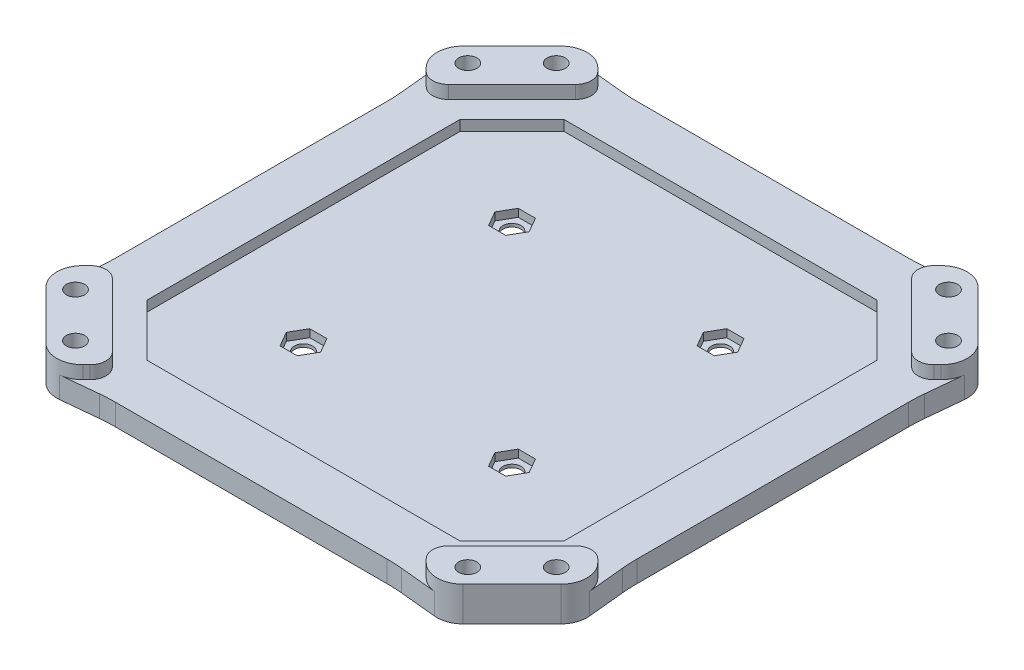
SolidWorks part; units mm, degrees
material "PP Copolymer"
ref_plane "Front Plane" through (0, 0, 0) normal (0, 0, 1) x (1, 0, 0)
ref_plane "Top Plane" through (0, 0, 0) normal (0, 1, 0) x (1, 0, 0)
ref_plane "Right Plane" through (0, 0, 0) normal (1, 0, 0) x (0, 0, -1)
sketch "Sketch1" plane through (0, 0, 0) normal (0, 1, 0) x (1, 0, 0)
  line L0 (50, 0) -> (-50, 0) construction
  line L1 (-50, -50) -> (50, -50) construction
  line L2 (-50, -50) -> (-50, 50) construction
  line L3 (-50, 50) -> (50, 50) construction
  line L4 (50, -50) -> (50, 50) construction
  line L5 (50, 50) -> (44.6967, 44.6967) construction
  line L6 (-50, 50) -> (50, -50) construction
  line L7 (0, 50) -> (0, -50) construction
  line L8 (-27.5164, 50) -> (27.5164, 50)
  line L9 (50, 27.5164) -> (50, -27.5164)
  line L10 (27.5164, -50) -> (-27.5164, -50)
  line L11 (-50, -27.5164) -> (-50, 27.5164)
  line L12 (37.6256, 46.1109) -> (46.1109, 37.6256) construction
  line L13 (38.3327, 51.0607) -> (51.0607, 38.3327)
  line L14 (27.5164, 50) -> (38.3327, 51.0607)
  line L15 (50, 27.5164) -> (51.0607, 38.3327)
  line L16 (50, -27.5164) -> (51.0607, -38.3327)
  line L17 (51.0607, -38.3327) -> (38.3327, -51.0607)
  line L18 (27.5164, -50) -> (38.3327, -51.0607)
  line L19 (-27.5164, -50) -> (-38.3327, -51.0607)
  line L20 (-38.3327, -51.0607) -> (-51.0607, -38.3327)
  line L21 (-50, -27.5164) -> (-51.0607, -38.3327)
  line L22 (-50, 27.5164) -> (-51.0607, 38.3327)
  line L23 (-51.0607, 38.3327) -> (-38.3327, 51.0607)
  line L24 (-27.5164, 50) -> (-38.3327, 51.0607)
  line L25 (41.8683, 41.8683) -> (44.6967, 44.6967) construction
  circle A0 centre (37.6256, 46.1109) radius 1.75
  circle A1 centre (46.1109, 37.6256) radius 1.75
  circle A2 centre (37.6256, -46.1109) radius 1.75
  circle A3 centre (46.1109, -37.6256) radius 1.75
  circle A4 centre (-46.1109, -37.6256) radius 1.75
  circle A5 centre (-37.6256, -46.1109) radius 1.75
  circle A6 centre (-37.6256, 46.1109) radius 1.75
  circle A7 centre (-46.1109, 37.6256) radius 1.75
  point P0 (0, 0)
  point P15 (0, 0)
  point P18 (0, 0)
  point P21 (0, 0)
  point P24 (0, 0)
  point P58 (0, 0)
  dimension "D12" = 3.5
  dimension "D3" = 92.2218
  dimension "D7" = 12
  dimension "D14" = 75.2513
  dimension "D15" = 75.2513
  dimension "D6" = 75.2513
  dimension "D1" = 100
  dimension "D2" = 100
  dimension "D4" = 7.5
  dimension "D5" = 45
  dimension "D8" = 12
  dimension "D9" = 18
  dimension "D10" = 4
  dimension "D11" = 18
  dimension "D13" = 5.601
extrude "Boss-Extrude1" add sketch "Sketch1" along normal blind 4.1 contours L8 L24 L23 L22 L11 L21 L20 L19 L10 L18 L17 L16 L9 L15 L13 L14 A7 A6 A5 A4 A3 A2 A1 A0 region at (0, 0, 0)
sketch "Sketch2" plane through (0, 4.1, 0) normal (0, 1, 0) x (1, 0, 0)
  line L0 (0, 0) -> (0, 40) construction
  line L2 (0, 0) -> (-40, 0) construction
  line L4 (-40, -30) -> (-40, 30)
  line L5 (-40, 30) -> (-30, 40)
  line L6 (-30, 40) -> (30, 40)
  line L7 (30, 40) -> (40, 30)
  line L8 (40, 30) -> (40, -30)
  line L9 (40, -30) -> (30, -40)
  line L10 (30, -40) -> (-30, -40)
  line L11 (-30, -40) -> (-40, -30)
  dimension "D1" = 80
  dimension "D2" = 80
  dimension "D3" = 45
  dimension "D4" = 90
  dimension "D5" = 60
  dimension "D6" = 45
extrude "Cut-Extrude1" cut sketch "Sketch2" against normal blind 2
sketch "Sketch3" plane through (0, 2.1, 0) normal (0, 1, 0) x (1, 0, 0)
  line L0 (0, 0) -> (-34, 0) construction
  line L18 (-29.0716, 13.612) -> (-21.0716, 6.8992)
  line L19 (-20, 4.6011) -> (-20, -4.6011)
  line L20 (-21.0716, -6.8992) -> (-29.0716, -13.612)
  line L21 (-34, 11.3139) -> (-34, -11.3139)
  line L22 (34, -11.3139) -> (34, 11.3139)
  line L23 (21.0716, 6.8992) -> (29.0716, 13.612)
  line L24 (20, -4.6011) -> (20, 4.6011)
  line L25 (29.0716, -13.612) -> (21.0716, -6.8992)
  line L26 (-14, -21.4596) -> (14, -21.4596)
  line L27 (9.5853, -8.5313) -> (16.2981, -16.5313)
  line L28 (-7.2872, -7.4596) -> (7.2872, -7.4596)
  line L29 (-16.2981, -16.5313) -> (-9.5853, -8.5313)
  line L30 (0, 10.4596) -> (0, -10.4596) construction
  line L31 (7.2872, -10.4596) -> (-7.2872, -10.4596) construction
  line L32 (7.2872, 10.4596) -> (-7.2872, 10.4596) construction
  line L33 (-16.2981, 16.5313) -> (-9.5853, 8.5313)
  line L34 (-7.2872, 7.4596) -> (7.2872, 7.4596)
  line L35 (9.5853, 8.5313) -> (16.2981, 16.5313)
  line L36 (-14, 21.4596) -> (14, 21.4596)
  line L37 (0, -10.4596) -> (0, -21.4596) construction
  arc A16 (-29.0716, -13.612) -> (-34, -11.3139) centre (-31, -11.3139) cw
  arc A17 (-20, -4.6011) -> (-21.0716, -6.8992) centre (-23, -4.6011) cw
  arc A18 (-21.0716, 6.8992) -> (-20, 4.6011) centre (-23, 4.6011) cw
  arc A19 (-29.0716, 13.612) -> (-34, 11.3139) centre (-31, 11.3139) ccw
  arc A20 (29.0716, -13.612) -> (34, -11.3139) centre (31, -11.3139) ccw
  arc A21 (29.0716, 13.612) -> (34, 11.3139) centre (31, 11.3139) cw
  arc A22 (20, 4.6011) -> (21.0716, 6.8992) centre (23, 4.6011) cw
  arc A23 (21.0716, -6.8992) -> (20, -4.6011) centre (23, -4.6011) cw
  arc A24 (-16.2981, -16.5313) -> (-14, -21.4596) centre (-14, -18.4596) ccw
  arc A25 (16.2981, -16.5313) -> (14, -21.4596) centre (14, -18.4596) cw
  arc A26 (7.2872, -7.4596) -> (9.5853, -8.5313) centre (7.2872, -10.4596) cw
  arc A27 (-9.5853, -8.5313) -> (-7.2872, -7.4596) centre (-7.2872, -10.4596) cw
  arc A28 (-9.5853, 8.5313) -> (-7.2872, 7.4596) centre (-7.2872, 10.4596) ccw
  arc A29 (7.2872, 7.4596) -> (9.5853, 8.5313) centre (7.2872, 10.4596) ccw
  arc A30 (16.2981, 16.5313) -> (14, 21.4596) centre (14, 18.4596) ccw
  arc A31 (-16.2981, 16.5313) -> (-14, 21.4596) centre (-14, 18.4596) cw
  point P53 (0, 0)
  point P57 (0, 0)
  dimension "D3" = 14
  dimension "D2" = 3
  dimension "D1" = 20
  dimension "D4" = 100
  dimension "D5" = 9.2022
  dimension "D6" = 50
  dimension "D7" = 46
  dimension "D8" = 62
  dimension "D9" = 62
  dimension "D10" = 50
  dimension "D11" = 7.4596
  dimension "D12" = 28
  dimension "D13" = 22.6277
extrude "Cut-Extrude2" [suppressed] cut sketch "Sketch3" against normal blind 1.5
sketch "Sketch4" plane through (0, 2.1, 0) normal (0, 1, 0) x (1, 0, 0)
  line L1 (0, 0) -> (30, 0) construction
  line L2 (0, 0) -> (0, 30) construction
  line L3 (0, 30) -> (30, 30) construction
  line L4 (30, 0) -> (30, 30) construction
  circle A0 centre (30, 30) radius 1.75
  dimension "D2" = 3.5
  dimension "D1" = 30
  dimension "D3" = 30
extrude "Cut-Extrude3" [suppressed] cut sketch "Sketch4" against normal through all
sketch "Sketch5" [suppressed] plane through (0, 2.1, 0) normal (0, 1, 0) x (1, 0, 0)
  circle A0 centre (30, 30) radius 4
  circle A1 centre (30, 30) radius 1.75 construction
  circle A2 centre (30, 30) radius 1.75
  dimension "D1" = 8
extrude "Boss-Extrude2" [suppressed] add sketch "Sketch5" along normal blind 1.5
ref_axis "Axis1" through (0, 4.2, 0) along (0, -1, 0)
fillet "Fillet2" radius 30 8 edges at (-50, 2.05, 27.5164) (-50, 2.05, -27.5164) (-27.5164, 2.05, -50) (27.5164, 2.05, -50) (50, 2.05, -27.5164) (50, 2.05, 27.5164) (-27.5164, 2.05, 50) (27.5164, 2.05, 50)
sketch "Sketch7" plane through (0, 2.1, 0) normal (0, 1, 0) x (1, 0, 0)
  line L1 (-10, -10) -> (10, -10)
  line L2 (-10, -10) -> (-10, 10)
  line L3 (-10, 10) -> (10, 10)
  line L4 (10, -10) -> (10, 10)
  line L5 (-10, -10) -> (10, 10) construction
  line L6 (-10, 10) -> (10, -10) construction
  point P0 (0, 0)
  dimension "D1" = 20
  dimension "D2" = 20
extrude "Cut-Extrude5" [suppressed] cut sketch "Sketch7" against normal through all
mirror "Simetría1" [suppressed] about plane through (0, 0, 0) normal (1, 0, 0)
mirror "Simetría2" [suppressed] about plane through (0, 0, 0) normal (0, 0, 1)
fillet "Redondeo1" [suppressed] radius 2
fillet "Redondeo2" radius 5 8 edges at (-38.3327, 2.05, 51.0607) (38.3327, 2.05, 51.0607) (51.0607, 2.05, 38.3327) (51.0607, 2.05, -38.3327) (38.3327, 2.05, -51.0607) (-51.0607, 2.05, 38.3327) (-51.0607, 2.05, -38.3327) (-38.3327, 2.05, -51.0607)
sketch "Croquis1" plane through (0, 4.1, 0) normal (0, 1, 0) x (1, 0, 0)
  line L0 (-18.4123, -17.25) -> (-16.8246, -20) construction
  line L1 (-23.1754, -20) -> (-21.5877, -22.75) construction
  line L2 (-18.4123, -17.25) -> (-21.5877, -17.25) construction
  line L3 (-21.5877, -17.25) -> (-23.1754, -20) construction
  line L4 (-21.5877, -22.75) -> (-18.4123, -22.75) construction
  line L5 (-18.4123, -22.75) -> (-16.8246, -20) construction
  line L6 (-18.4123, -22.75) -> (-21.5877, -17.25) construction
  line L7 (-18.4123, -17.25) -> (-21.5877, -22.75) construction
  line L8 (-16.8246, -20) -> (-23.1754, -20) construction
  line L9 (-18.3546, -17.15) -> (-16.7091, -20)
  line L10 (-18.3546, -22.85) -> (-16.7091, -20)
  line L11 (-21.6454, -22.85) -> (-18.3546, -22.85)
  line L12 (-23.2909, -20) -> (-21.6454, -22.85)
  line L13 (-21.6454, -17.15) -> (-23.2909, -20)
  line L14 (-18.3546, -17.15) -> (-21.6454, -17.15)
  point P3 (-20, -20)
  dimension "D1" = 3.1754
  dimension "D2" = 5.5
  dimension "D3" = 20
  dimension "D4" = 3.2909
  dimension "D5" = 6.5818
  dimension "D6" = 0.1
  dimension "D7" = 20
extrude "Cortar-Extruir1" cut sketch "Croquis1" against normal blind 3.5
mirror "Simetría3" about plane through (0, 0, 0) normal (1, 0, 0) of "Cortar-Extruir1"
mirror "Simetría4" about plane through (0, 0, 0) normal (0, 0, 1) of "Simetría3"
sketch "Croquis2" plane through (0, 2.1, 0) normal (0, 1, 0) x (1, 0, 0)
  line L0 (0, 0) -> (0, -20) construction
  circle A0 centre (-20, -20) radius 1.75
  circle A1 centre (-20, 20) radius 1.75
  circle A2 centre (20, 20) radius 1.75
  circle A3 centre (20, -20) radius 1.75
  dimension "D1" = 40
  dimension "D3" = 3.5
  dimension "D2" = 40
extrude "Cortar-Extruir2" cut sketch "Croquis2" against normal blind 2.5
sketch "Croquis3" plane through (0, 4.1, 0) normal (0, 1, 0) x (1, 0, 0)
  line L0 (-49.3894, 32.9329) -> (-48.6823, 32.2258)
  line L1 (-44.4397, 32.2258) -> (-32.2258, 44.4397)
  line L2 (-32.2258, 48.6823) -> (-32.9329, 49.3894)
  line L3 (-2.255, 0) -> (2.255, 0) construction
  line L4 (-40.004, -49.3894) -> (-49.3894, -40.004)
  line L5 (-32.2258, -48.6823) -> (-32.9329, -49.3894)
  line L6 (-44.4397, -32.2258) -> (-32.2258, -44.4397)
  line L7 (-49.3894, -32.9329) -> (-48.6823, -32.2258)
  line L8 (0, -2.255) -> (0, 2.255) construction
  line L9 (40.004, 49.3894) -> (49.3894, 40.004)
  line L10 (49.3894, -32.9329) -> (48.6823, -32.2258)
  line L11 (44.4397, -32.2258) -> (32.2258, -44.4397)
  line L12 (32.2258, -48.6823) -> (32.9329, -49.3894)
  line L13 (40.004, -49.3894) -> (49.3894, -40.004)
  line L14 (32.2258, 48.6823) -> (32.9329, 49.3894)
  line L15 (44.4397, 32.2258) -> (32.2258, 44.4397)
  line L16 (-49.3894, -40.004) -> (-40.004, -49.3894)
  line L17 (-35.9805, -50.83) -> (-28.9768, -50.1432)
  line L18 (-26.049, -50) -> (26.049, -50)
  line L19 (28.9768, -50.1432) -> (35.9805, -50.83)
  line L20 (40.004, -49.3894) -> (49.3894, -40.004)
  line L21 (50.83, -35.9805) -> (50.1432, -28.9768)
  line L22 (50, -26.049) -> (50, 26.049)
  line L23 (50.1432, 28.9768) -> (50.83, 35.9805)
  line L24 (49.3894, 40.004) -> (40.004, 49.3894)
  line L25 (35.9805, 50.83) -> (28.9768, 50.1432)
  line L26 (26.049, 50) -> (-26.049, 50)
  line L27 (-28.9768, 50.1432) -> (-35.9805, 50.83)
  line L28 (-40.004, 49.3894) -> (-49.3894, 40.004)
  line L29 (-50.83, 35.9805) -> (-50.1432, 28.9768)
  line L30 (-50, 26.049) -> (-50, -26.049)
  line L31 (-50.1432, -28.9768) -> (-50.83, -35.9805)
  line L44 (-40.004, 49.3894) -> (-49.3894, 40.004)
  line L48 (49.3894, 32.9329) -> (48.6823, 32.2258)
  circle A3 centre (-37.6256, 46.1109) radius 1.75 construction
  circle A4 centre (-46.1109, 37.6256) radius 1.75 construction
  arc A5 (-32.2258, 44.4397) -> (-32.2258, 48.6823) centre (-34.3471, 46.561) ccw
  arc A6 (-48.6823, 32.2258) -> (-44.4397, 32.2258) centre (-46.561, 34.3471) ccw
  circle A8 centre (-37.6256, 46.1109) radius 1.75
  circle A9 centre (-46.1109, 37.6256) radius 1.75
  arc A16 (-40.004, -49.3894) -> (-35.9805, -50.83) centre (-36.4685, -45.8539) ccw
  arc A17 (-26.049, -50) -> (-28.9768, -50.1432) centre (-26.049, -80) ccw
  arc A18 (28.9768, -50.1432) -> (26.049, -50) centre (26.049, -80) ccw
  arc A19 (35.9805, -50.83) -> (40.004, -49.3894) centre (36.4685, -45.8539) ccw
  arc A20 (49.3894, -40.004) -> (50.83, -35.9805) centre (45.8539, -36.4685) ccw
  arc A21 (50, -26.049) -> (50.1432, -28.9768) centre (80, -26.049) ccw
  arc A22 (50.1432, 28.9768) -> (50, 26.049) centre (80, 26.049) ccw
  arc A23 (50.83, 35.9805) -> (49.3894, 40.004) centre (45.8539, 36.4685) ccw
  arc A24 (40.004, 49.3894) -> (35.9805, 50.83) centre (36.4685, 45.8539) ccw
  arc A25 (26.049, 50) -> (28.9768, 50.1432) centre (26.049, 80) ccw
  arc A26 (-28.9768, 50.1432) -> (-26.049, 50) centre (-26.049, 80) ccw
  arc A27 (-35.9805, 50.83) -> (-40.004, 49.3894) centre (-36.4685, 45.8539) ccw
  arc A28 (-49.3894, 40.004) -> (-50.83, 35.9805) centre (-45.8539, 36.4685) ccw
  arc A29 (-50, 26.049) -> (-50.1432, 28.9768) centre (-80, 26.049) ccw
  arc A30 (-50.1432, -28.9768) -> (-50, -26.049) centre (-80, -26.049) ccw
  arc A31 (-50.83, -35.9805) -> (-49.3894, -40.004) centre (-45.8539, -36.4685) ccw
  arc A43 (-32.9329, 49.3894) -> (-40.004, 49.3894) centre (-36.4685, 45.8539) ccw
  arc A44 (-49.3894, 40.004) -> (-49.3894, 32.9329) centre (-45.8539, 36.4685) ccw
  arc A48 (-49.3894, -40.004) -> (-49.3894, -32.9329) centre (-45.8539, -36.4685) cw
  arc A49 (-32.9329, -49.3894) -> (-40.004, -49.3894) centre (-36.4685, -45.8539) cw
  circle A50 centre (-46.1109, -37.6256) radius 1.75
  circle A51 centre (-37.6256, -46.1109) radius 1.75
  arc A52 (-48.6823, -32.2258) -> (-44.4397, -32.2258) centre (-46.561, -34.3471) cw
  arc A53 (-32.2258, -44.4397) -> (-32.2258, -48.6823) centre (-34.3471, -46.561) cw
  arc A54 (32.2258, -44.4397) -> (32.2258, -48.6823) centre (34.3471, -46.561) ccw
  arc A55 (48.6823, -32.2258) -> (44.4397, -32.2258) centre (46.561, -34.3471) ccw
  circle A56 centre (37.6256, -46.1109) radius 1.75
  circle A57 centre (46.1109, -37.6256) radius 1.75
  arc A58 (32.9329, -49.3894) -> (40.004, -49.3894) centre (36.4685, -45.8539) ccw
  arc A59 (49.3894, -40.004) -> (49.3894, -32.9329) centre (45.8539, -36.4685) ccw
  arc A60 (49.3894, 40.004) -> (49.3894, 32.9329) centre (45.8539, 36.4685) cw
  arc A61 (32.9329, 49.3894) -> (40.004, 49.3894) centre (36.4685, 45.8539) cw
  circle A62 centre (46.1109, 37.6256) radius 1.75
  circle A63 centre (37.6256, 46.1109) radius 1.75
  arc A64 (48.6823, 32.2258) -> (44.4397, 32.2258) centre (46.561, 34.3471) cw
  arc A65 (32.2258, 44.4397) -> (32.2258, 48.6823) centre (34.3471, 46.561) cw
  dimension "D2" = 9
  dimension "D3" = 3
  dimension "D1" = 0
extrude "Saliente-Extruir1" add sketch "Croquis3" along normal blind 2.5
